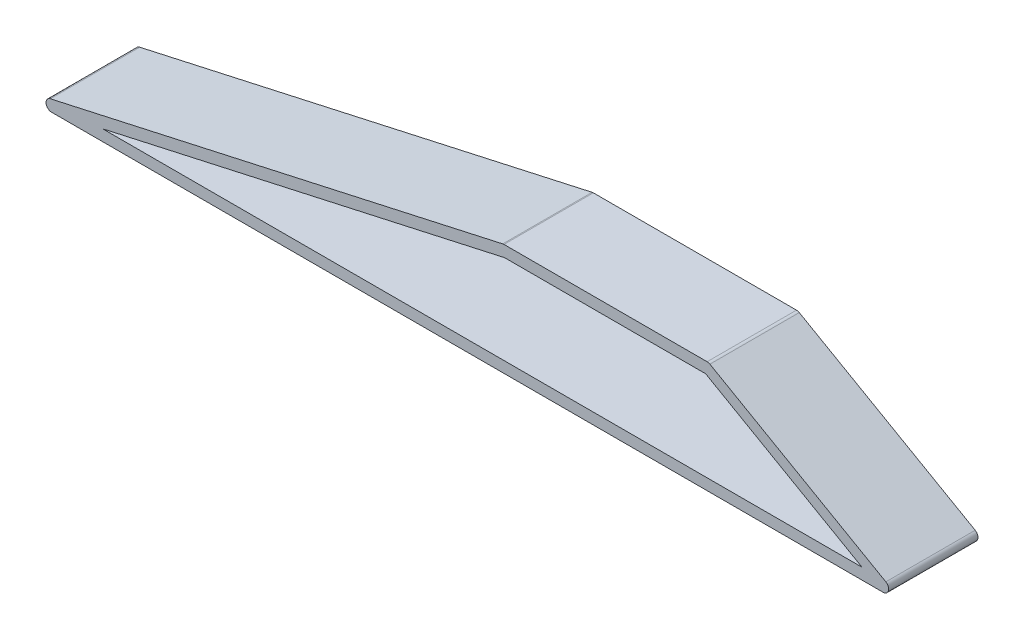
SolidWorks part; units mm, degrees
ref_plane "Front Plane" through (0, 0, 0) normal (0, 0, 1) x (1, 0, 0)
ref_plane "Top Plane" through (0, 0, 0) normal (0, 1, 0) x (1, 0, 0)
ref_plane "Right Plane" through (0, 0, 0) normal (1, 0, 0) x (0, 0, -1)
sketch "Sketch1" plane through (0, 0, 0) normal (0, 0, 1) x (1, 0, 0)
  line L0 (0, 0) -> (215.9, 0)
  line L1 (215.9, 0) -> (171.45, 25.4)
  line L2 (171.45, 25.4) -> (114.3, 25.4)
  line L3 (114.3, 25.4) -> (0, 0)
  line L4 (113.9515, 28.575) -> (-28.9235, -3.175)
  line L5 (-28.9235, -3.175) -> (227.8557, -3.175)
  line L6 (227.8557, -3.175) -> (172.2932, 28.575)
  line L7 (172.2932, 28.575) -> (113.9515, 28.575)
  dimension "D1" = 44.45
  dimension "D2" = 57.15
  dimension "D3" = 215.9
  dimension "D4" = 25.4
  dimension "D5" = 3.175
extrude "Boss-Extrude1" add sketch "Sketch1" along normal blind 25.4
fillet "Fillet1" radius 1.5875 4 edges at (-28.9235, -3.175, 12.7) (113.9515, 28.575, 12.7) (172.2932, 28.575, 12.7) (227.8557, -3.175, 12.7)
